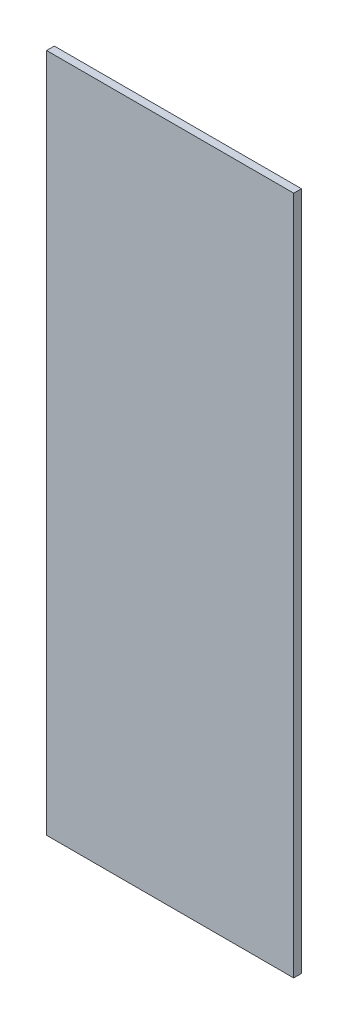
SolidWorks part; units mm, degrees
ref_plane "Front Plane" through (0, 0, 0) normal (0, 0, 1) x (1, 0, 0)
ref_plane "Top Plane" through (0, 0, 0) normal (0, 1, 0) x (1, 0, 0)
ref_plane "Right Plane" through (0, 0, 0) normal (1, 0, 0) x (0, 0, -1)
sketch "Sketch2" plane through (0, 0, 0) normal (0, 0, 1) x (1, 0, 0)
  line L1 (0, 0) -> (50.8, 0)
  line L2 (0, 0) -> (0, 139.7)
  line L3 (0, 139.7) -> (50.8, 139.7)
  line L4 (50.8, 0) -> (50.8, 139.7)
  dimension "D1" = 50.8
  dimension "D2" = 139.7
extrude "Boss-Extrude1" add sketch "Sketch2" along normal blind 1.5875
